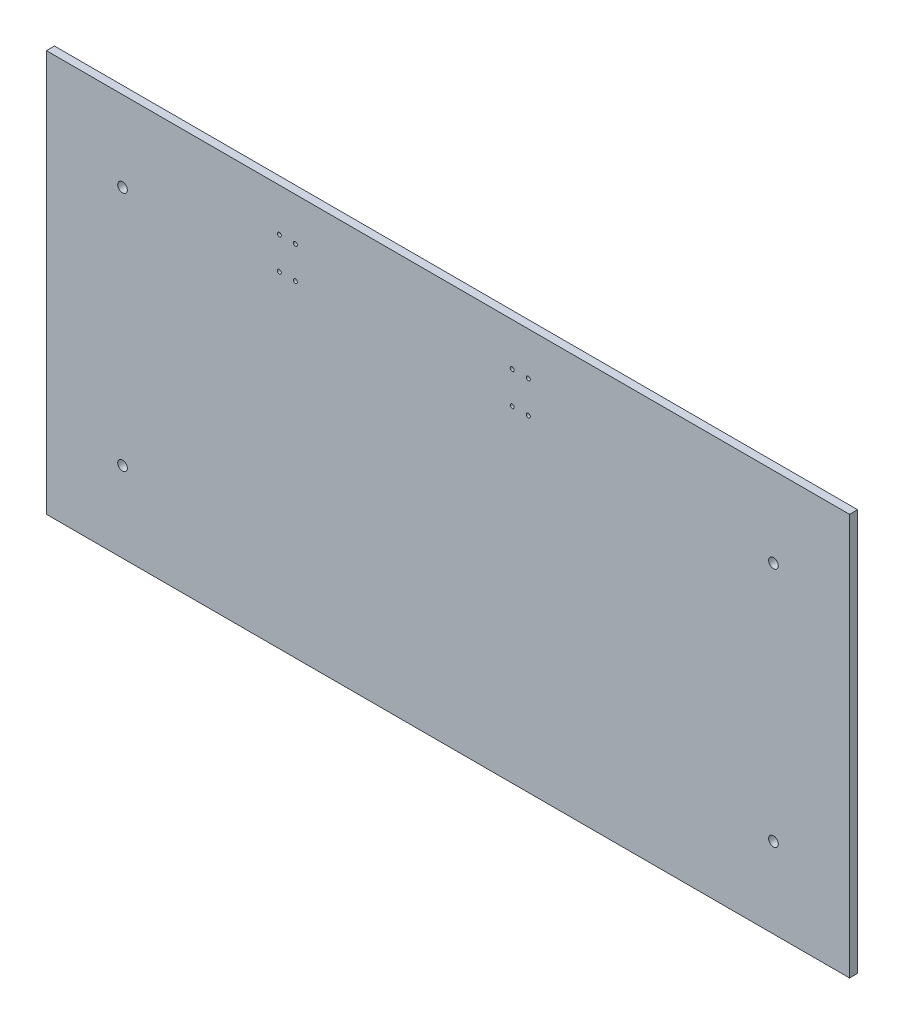
SolidWorks part; units mm, degrees
ref_plane "Front Plane" through (0, 0, 0) normal (0, 0, 1) x (1, 0, 0)
ref_plane "Top Plane" through (0, 0, 0) normal (0, 1, 0) x (1, 0, 0)
ref_plane "Right Plane" through (0, 0, 0) normal (1, 0, 0) x (0, 0, -1)
sketch "Sketch1" plane through (0, 0, 0) normal (0, 0, 1) x (1, 0, 0)
  line L1 (-1055.3215, 908.1778) -> (-55.3215, 908.1778)
  line L2 (-1055.3215, 908.1778) -> (-1055.3215, 408.1778)
  line L3 (-1055.3215, 408.1778) -> (-55.3215, 408.1778)
  line L4 (-55.3215, 908.1778) -> (-55.3215, 408.1778)
  line L5 (-1055.3215, 908.1778) -> (-55.3215, 408.1778) construction
  line L6 (-1055.3215, 408.1778) -> (-55.3215, 908.1778) construction
  point P0 (-555.3215, 658.1778)
  dimension "D1" = 1000
  dimension "D2" = 500
extrude "Boss-Extrude1" add sketch "Sketch1" along normal blind 10
sketch "Sketch2" plane through (0, 0, 10) normal (0, 0, 1) x (1, 0, 0)
  line L0 (-555.3215, 908.1778) -> (-555.3215, 408.1778) construction
  line L1 (-765.3215, 854.6978) -> (-455.3215, 854.6978) construction
  line L2 (-610.3215, 875.149) -> (-610.3215, 837.6017) construction
  line L3 (-55.3215, 908.1778) -> (-1055.3215, 908.1778) construction
  line L6 (-1055.3215, 408.1778) -> (-55.3215, 408.1778) construction
  line L7 (-1055.3215, 658.1778) -> (-55.3215, 658.1778) construction
  line L8 (-1055.3215, 908.1778) -> (-1055.3215, 408.1778) construction
  line L9 (-55.3215, 408.1778) -> (-55.3215, 908.1778) construction
  circle A10 centre (-960.5715, 808.1778) radius 6
  circle A11 centre (-960.5715, 508.1778) radius 6
  circle A12 centre (-150.0715, 508.1778) radius 6
  circle A13 centre (-150.0715, 808.1778) radius 6
  circle A14 centre (-765.3215, 854.6978) radius 2.5
  circle A15 centre (-745.3215, 854.6978) radius 2.5
  circle A16 centre (-765.3215, 814.6978) radius 2.5
  circle A17 centre (-745.3215, 814.6978) radius 2.5
  circle A18 centre (-475.3215, 814.6978) radius 2.5
  circle A19 centre (-455.3215, 814.6978) radius 2.5
  circle A20 centre (-475.3215, 854.6978) radius 2.5
  circle A21 centre (-455.3215, 854.6978) radius 2.5
  dimension "D1" = 12
  dimension "D2" = 12
  dimension "D6" = 5
  dimension "D7" = 5
  dimension "D8" = 5
  dimension "D9" = 5
  dimension "D3" = 150
  dimension "D4" = 300
  dimension "D5" = 405.25
  dimension "D10" = 290
  dimension "D11" = 20
  dimension "D12" = 290
  dimension "D13" = 20
  dimension "D14" = 53.48
  dimension "D15" = 40
  dimension "D16" = 290
extrude "Cut-Extrude1" cut sketch "Sketch2" against normal through all
sketch "Sketch3" plane through (-55.3215, 0, 0) normal (1, 0, 0) x (0, 0, -1)
  line L0 (-10, 408.1778) -> (-10, 908.1778) construction
  line L1 (-10, 808.1778) -> (0, 808.1778)
  line L2 (-10, 808.1778) -> (-10, 608.1778)
  line L3 (-10, 608.1778) -> (0, 608.1778)
  line L4 (0, 808.1778) -> (0, 608.1778)
  line L5 (0, 408.1778) -> (0, 908.1778) construction
  line L6 (-10, 408.1778) -> (0, 408.1778) construction
  dimension "D1" = 200
  dimension "D2" = 200
extrude "Boss-Extrude2" add sketch "Sketch3" along normal blind 300
sketch "Sketch4" plane through (0, 0, 10) normal (0, 0, 1) x (1, 0, 0)
  line L0 (244.6785, 708.1778) -> (57.9689, 708.1778) construction
  line L1 (244.6785, 808.1778) -> (244.6785, 608.1778) construction
  circle A0 centre (184.6785, 708.1778) radius 5
  circle A1 centre (159.6785, 708.1778) radius 5
  dimension "D1" = 10
  dimension "D2" = 25
  dimension "D3" = 60
extrude "Cut-Extrude2" cut sketch "Sketch4" against normal blind 10
sketch "Sketch7" plane through (0, 608.1778, 0) normal (0, -1, 0) x (1, 0, 0)
  line L1 (-55.3215, 10) -> (252.1192, 10)
  line L2 (-55.3215, 10) -> (-55.3215, -32.5792)
  line L3 (-55.3215, -32.5792) -> (252.1192, -32.5792)
  line L4 (252.1192, 10) -> (252.1192, -32.5792)
extrude "Cut-Extrude5" cut sketch "Sketch7" against normal blind 1300
